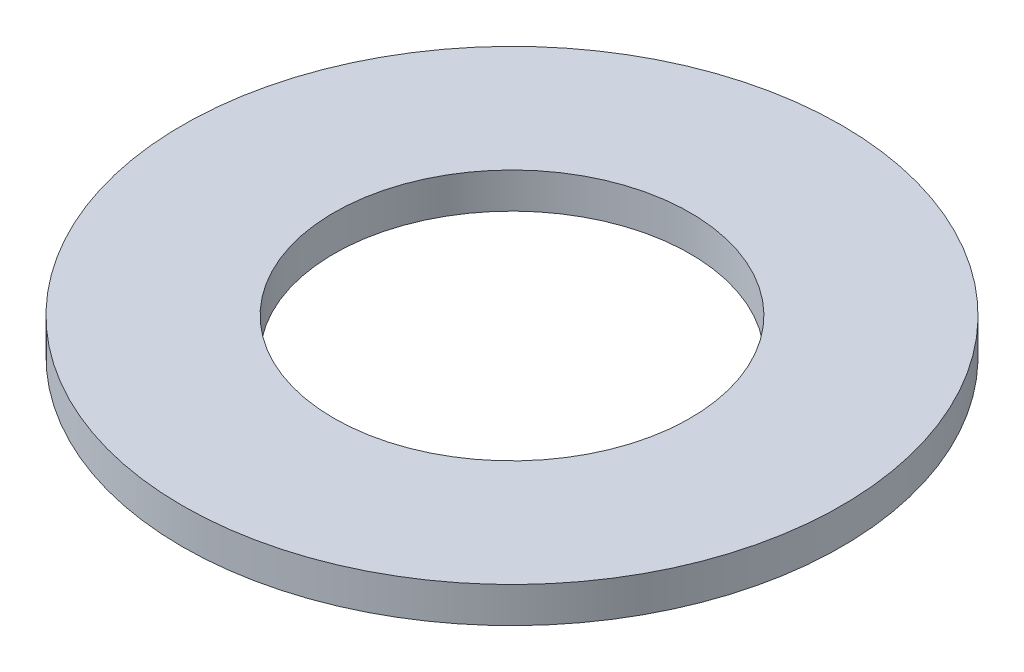
SolidWorks part; units mm, degrees
ref_plane "Front Plane" through (0, 0, 0) normal (0, 0, 1) x (1, 0, 0)
ref_plane "Top Plane" through (0, 0, 0) normal (0, 1, 0) x (1, 0, 0)
ref_plane "Right Plane" through (0, 0, 0) normal (1, 0, 0) x (0, 0, -1)
sketch "Sketch1" plane through (0, 0, 0) normal (0, 1, 0) x (1, 0, 0)
  circle A0 centre (0, 0) radius 92.5
  dimension "FLANGE_OD" = 185
extrude "Boss-Extrude1" add sketch "Sketch1" along normal blind 10
sketch "Sketch2" plane through (0, 0, 0) normal (0, 1, 0) x (1, 0, 0)
  circle A0 centre (0, 0) radius 50
  dimension "BORE_D" = 100
extrude "Cut-Extrude1" cut sketch "Sketch2" along normal through all
sketch "Sketch3" plane through (0, 10, 0) normal (0, 1, 0) x (1, 0, 0)
  circle A0 centre (0, 0) radius 39.0257 construction
  circle A1 centre (-39.0257, 0) radius 4.4605
  dimension "BOLT_D" = 8.9211
  dimension "BOLT_PCD" = 78.0514
extrude "Cut-Extrude2" cut sketch "Sketch3" against normal blind 8.4248 rebuild error yes
pattern_circular "CirPattern1" count 6 over 360 rebuild error yes
